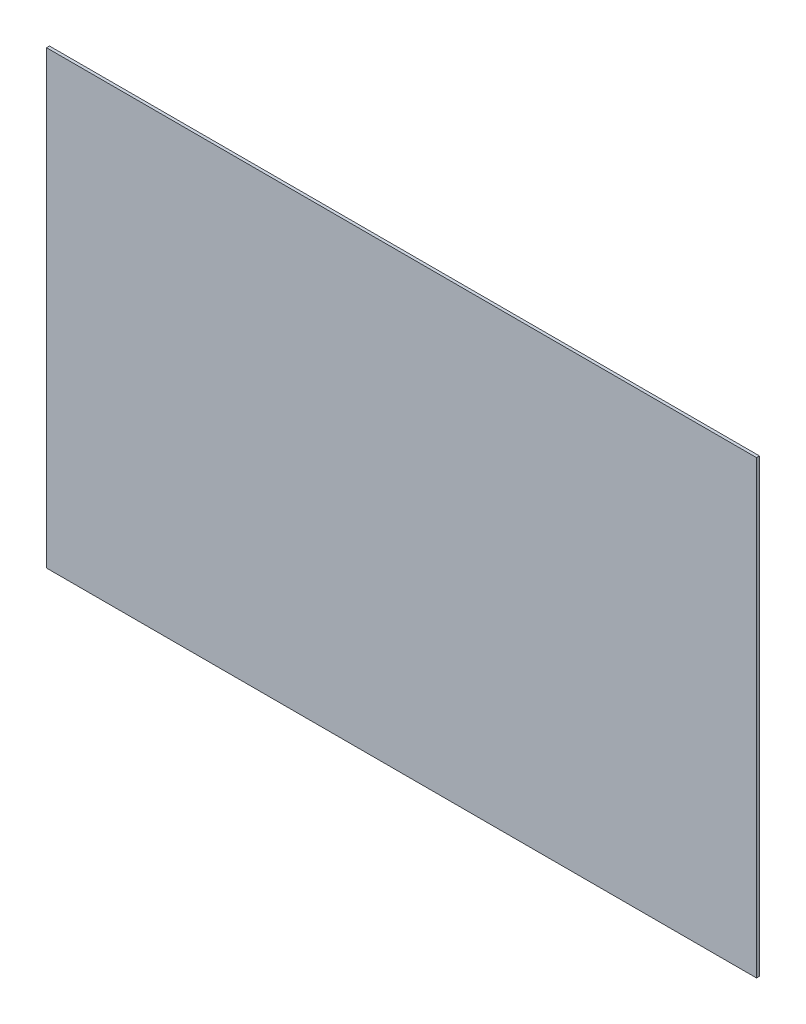
SolidWorks part; units mm, degrees
material "Mahogany"
ref_plane "Front Plane" through (0, 0, 0) normal (0, 0, 1) x (1, 0, 0)
ref_plane "Top Plane" through (0, 0, 0) normal (0, 1, 0) x (1, 0, 0)
ref_plane "Right Plane" through (0, 0, 0) normal (1, 0, 0) x (0, 0, -1)
sketch "Sketch1" plane through (0, 0, 0) normal (0, 0, 1) x (1, 0, 0)
  line L1 (-382.5, 242.8) -> (382.5, 242.8)
  line L2 (-382.5, 242.8) -> (-382.5, -242.8)
  line L3 (-382.5, -242.8) -> (382.5, -242.8)
  line L4 (382.5, 242.8) -> (382.5, -242.8)
  line L5 (-382.5, 242.8) -> (382.5, -242.8) construction
  line L6 (-382.5, -242.8) -> (382.5, 242.8) construction
  point P0 (0, 0)
  dimension "D1" = 765
  dimension "D2" = 485.6
extrude "Boss-Extrude1" add sketch "Sketch1" along normal blind 3.175
equation "\"W\"= 1700"
equation "\"L\"= 780"
equation "\"H\"= 780"
equation "\"ARM_BOLT_SPACING\"= 166"
equation "\"ARM_TO_WALL\"= 200"
equation "\"D1@Sketch1\"=\"L\"-15"
equation "\"D2@Sketch1\"=\"H\"-(15+279.4)"
